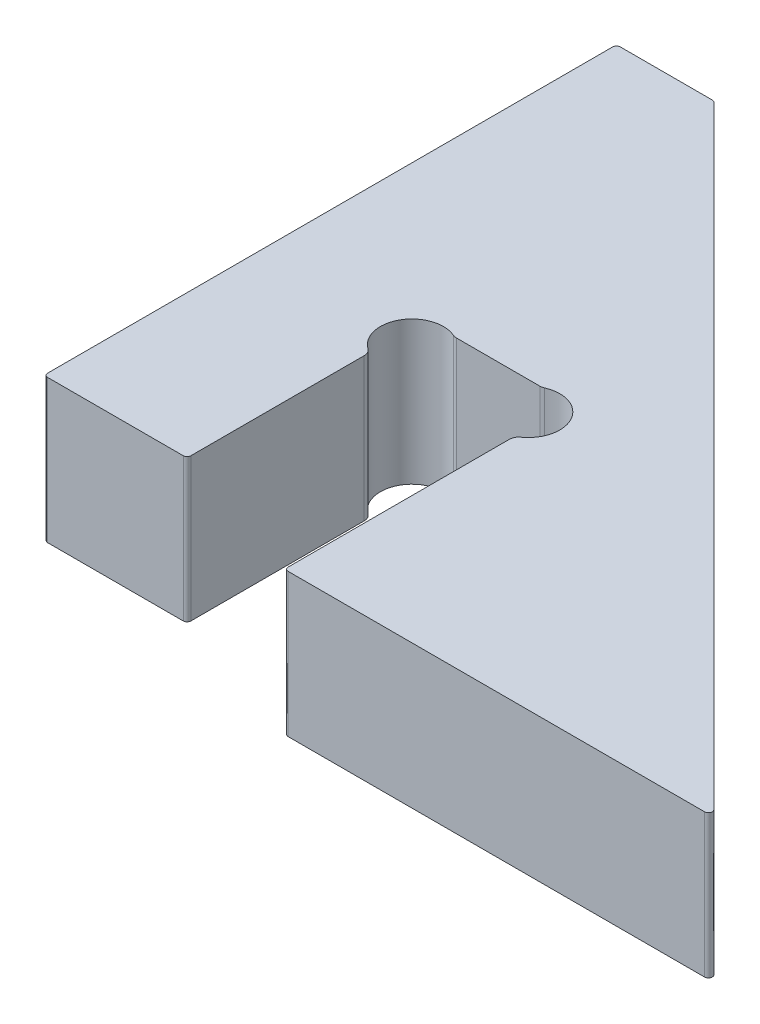
SolidWorks part; units mm, degrees
material "PE High Density"
ref_plane "Front Plane" through (0, 0, 0) normal (0, 0, 1) x (1, 0, 0)
ref_plane "Top Plane" through (0, 0, 0) normal (0, 1, 0) x (1, 0, 0)
ref_plane "Right Plane" through (0, 0, 0) normal (1, 0, 0) x (0, 0, -1)
other "Bounding Box"
ref_plane "Default Plane" through (13.8565, 3.175, 6.7999) normal (0, -1, 0) x (-1, 0, 0)
sketch "Sketch1" plane through (0, 0, 0) normal (0, 1, 0) x (1, 0, 0)
  line L0 (0, 0) -> (0, -25.4)
  line L1 (0, -25.4) -> (9.525, -25.4)
  line L2 (9.525, -25.4) -> (9.525, -12.7)
  line L3 (9.525, -12.7) -> (19.177, -12.7)
  line L4 (19.177, -12.7) -> (19.177, -25.4)
  line L5 (19.177, -25.4) -> (25.527, -19.05)
  line L6 (25.527, -19.05) -> (25.527, -6.35)
  line L8 (0, -12.7) -> (9.525, -12.7) construction
  line L9 (19.177, -12.7) -> (25.527, -12.7) construction
  line L10 (25.527, -6.35) -> (19.177, 0)
  line L11 (19.177, 0) -> (0, 0)
  point P7 (0, -12.7)
  dimension "D1" = 9.652
  dimension "D2" = 25.4
  dimension "D3" = 45
  dimension "D4" = 6.35
  dimension "D5" = 9.525
extrude "Boss-Extrude1" add sketch "Sketch1" along normal blind 9.525
sketch "Sketch2" plane through (0, 9.525, 0) normal (0, 1, 0) x (1, 0, 0)
  line L0 (19.177, 0) -> (44.577, -25.4)
  line L1 (44.577, -25.4) -> (19.177, -25.4)
  line L2 (19.177, -25.4) -> (19.177, -12.7)
  line L8 (19.177, -12.7) -> (0, 0)
  line L10 (25.527, -6.35) -> (19.177, 0) construction
  line L11 (0, 0) -> (0, 12.7)
  line L12 (6.477, 12.7) -> (19.177, 0)
  line L14 (0, 12.7) -> (6.477, 12.7)
  dimension "D1" = 12.7
extrude "Boss-Extrude2" add sketch "Sketch2" against normal through all
sketch "Sketch3" [suppressed] plane through (0, 9.525, 0) normal (0, 1, 0) x (1, 0, 0)
  line L2 (15.875, -19.05) -> (15.875, 0) construction
  line L6 (19.05, -3.175) -> (24.13, -3.175) construction
  line L7 (22.225, -6.35) -> (15.875, 0) construction
  line L8 (15.875, 0) -> (18.0026, 2.3567)
  line L9 (15.875, 0) -> (15.875, -3.175)
  line L10 (30.2574, -8.7067) -> (22.225, -17.6042)
  line L11 (22.225, -31.75) -> (22.225, -6.35) construction
  line L12 (22.225, -17.6042) -> (22.225, -11.2072)
  circle A1 centre (24.13, -3.175) radius 2.9845
  arc A2 (15.875, -3.175) -> (22.225, -11.2072) centre (24.13, -3.175) ccw
  arc A3 (30.2574, -8.7067) -> (18.0026, 2.3567) centre (24.13, -3.175) ccw
  dimension "D1" = 8.255
  dimension "D2" = 5.969
extrude "Boss-Extrude3" [suppressed] add sketch "Sketch3" against normal through all
sketch "Sketch7" [suppressed] plane through (0, 9.525, 0) normal (0, 1, 0) x (1, 0, 0)
  line L0 (15.875, 0) -> (0, 0) construction
  line L1 (15.875, -38.1) -> (34.925, -38.1)
  line L2 (15.875, -38.1) -> (15.875, 0)
  line L3 (15.875, 0) -> (34.925, 0)
  line L4 (34.925, -38.1) -> (34.925, 0)
  line L5 (15.875, -38.1) -> (34.925, 0) construction
  line L6 (15.875, 0) -> (34.925, -38.1) construction
  point P4 (25.4, -19.05)
  dimension "D1" = 19.05
extrude "Boss-Extrude5" [suppressed] add sketch "Sketch7" against normal through all
sketch "Sketch8" [suppressed] plane through (0, 9.525, 0) normal (0, 1, 0) x (1, 0, 0)
  line L0 (20.6375, -38.1) -> (20.6375, -28.575) construction
  line L1 (15.875, -38.1) -> (34.925, -38.1) construction
  line L2 (20.6375, -28.575) -> (30.1625, -28.575) construction
  line L3 (30.1625, -28.575) -> (30.1625, -9.525) construction
  line L4 (30.1625, -9.525) -> (20.6375, -9.525) construction
  line L5 (20.6375, -9.525) -> (20.6375, -28.575) construction
  line L6 (20.6375, -28.575) -> (15.875, -28.575) construction
  line L7 (15.875, -19.05) -> (15.875, -38.1) construction
  line L8 (34.925, -9.525) -> (30.1625, -9.525) construction
  line L9 (34.925, -38.1) -> (34.925, 0) construction
  line L10 (30.1625, -9.525) -> (30.1625, 0) construction
  line L11 (34.925, 0) -> (0, 0) construction
  line L12 (15.875, 0) -> (34.925, -4.7625)
  line L13 (15.875, 0) -> (34.925, 0)
  line L14 (34.925, 0) -> (34.925, -4.7625)
  line L15 (15.875, -38.1) -> (34.925, -33.3375)
  line L16 (34.925, -33.3375) -> (34.925, -38.1)
  line L17 (34.925, -38.1) -> (15.875, -38.1)
  line L18 (30.1625, -28.575) -> (30.1625, -33.3375) construction
  line L19 (30.1625, -33.3375) -> (34.925, -33.3375) construction
  circle A0 centre (20.6375, -9.525) radius 1.3891
  circle A1 centre (30.1625, -9.525) radius 1.3891
  circle A2 centre (30.1625, -28.575) radius 1.3891
  circle A3 centre (20.6375, -28.575) radius 1.3891
  dimension "D1" = 2.7781
  dimension "D2" = 4.7625
  dimension "D3" = 19.05
extrude "Cut-Extrude3" [suppressed] cut sketch "Sketch8" against normal through all
sketch "Sketch5" plane through (0, 9.525, 0) normal (0, 1, 0) x (1, 0, 0)
  line L0 (9.525, -12.7) -> (10.4775, -14.5665) construction
  line L1 (10.4775, -14.5665) -> (11.43, -12.7) construction
  line L2 (9.525, -12.7) -> (19.177, -12.7) construction
  line L3 (17.272, -12.7) -> (18.2245, -14.5665) construction
  line L4 (18.2245, -14.5665) -> (19.177, -12.7) construction
  line L5 (10.4775, -14.5665) -> (18.2245, -14.5665) construction
  circle A0 centre (18.2245, -14.5665) radius 2.0955
  circle A1 centre (10.4775, -14.5665) radius 2.0955
  dimension "D1" = 4.191
  dimension "D2" = 7.747
extrude "Cut-Extrude2" [suppressed] cut sketch "Sketch5" against normal through all
sketch "Sketch9" plane through (0, 9.525, 0) normal (0, 1, 0) x (1, 0, 0)
  line L0 (19.177, -12.7) -> (19.177, -25.4) construction
  line L1 (9.525, -12.7) -> (19.177, -12.7)
  line L2 (9.525, -12.7) -> (9.525, -9.525)
  line L3 (9.525, -9.525) -> (19.177, -9.525)
  line L4 (19.177, -12.7) -> (19.177, -9.525)
  line L5 (0, -25.4) -> (9.525, -25.4) construction
  dimension "D1" = 15.875
extrude "Cut-Extrude4" cut sketch "Sketch9" against normal through all
sketch "Sketch10" plane through (0, 9.525, 0) normal (0, 1, 0) x (1, 0, 0)
  line L0 (9.525, -9.525) -> (10.4775, -11.3915) construction
  line L1 (10.4775, -11.3915) -> (11.43, -9.525) construction
  line L2 (19.177, -9.525) -> (9.525, -9.525) construction
  line L3 (17.272, -9.525) -> (18.2245, -11.3915) construction
  line L4 (18.2245, -11.3915) -> (19.177, -9.525) construction
  line L5 (10.4775, -11.3915) -> (18.2245, -11.3915) construction
  circle A0 centre (10.4775, -11.3915) radius 2.0955
  circle A1 centre (18.2245, -11.3915) radius 2.0955
  dimension "D1" = 4.191
  dimension "D2" = 7.747
extrude "Cut-Extrude5" cut sketch "Sketch10" against normal through all
sketch "Sketch11" plane through (0, 9.525, 0) normal (0, 1, 0) x (1, 0, 0)
  line L0 (19.177, -25.4) -> (19.177, -28.575)
  line L1 (19.177, -28.575) -> (47.752, -28.575)
  line L2 (47.752, -28.575) -> (44.577, -25.4)
  line L3 (44.577, -25.4) -> (19.177, -25.4)
  line L4 (44.577, -25.4) -> (6.477, 12.7) construction
  dimension "D1" = 3.175
extrude "Boss-Extrude6" add sketch "Sketch11" against normal through all
fillet "Fillet1" [suppressed] radius 1.27
fillet "Fillet2" [suppressed] radius 1.27
fillet "Fillet4" radius 0.254 6 edges at (0, 4.7625, 25.4) (9.525, 4.7625, 25.4) (0, 4.7625, -12.7) (6.477, 4.7625, -12.7) (47.752, 4.7625, 28.575) (19.177, 4.7625, 28.575)
fillet "Fillet5" [suppressed] radius 0.254
fillet "Fillet6" [suppressed] radius 0.254
fillet "Fillet7" [suppressed] radius 2.54
fillet "Fillet8" radius 0.635 4 edges at (19.177, 4.7625, 13.258) (9.525, 4.7625, 13.258) (17.272, 4.7625, 9.525) (11.43, 4.7625, 9.525)
